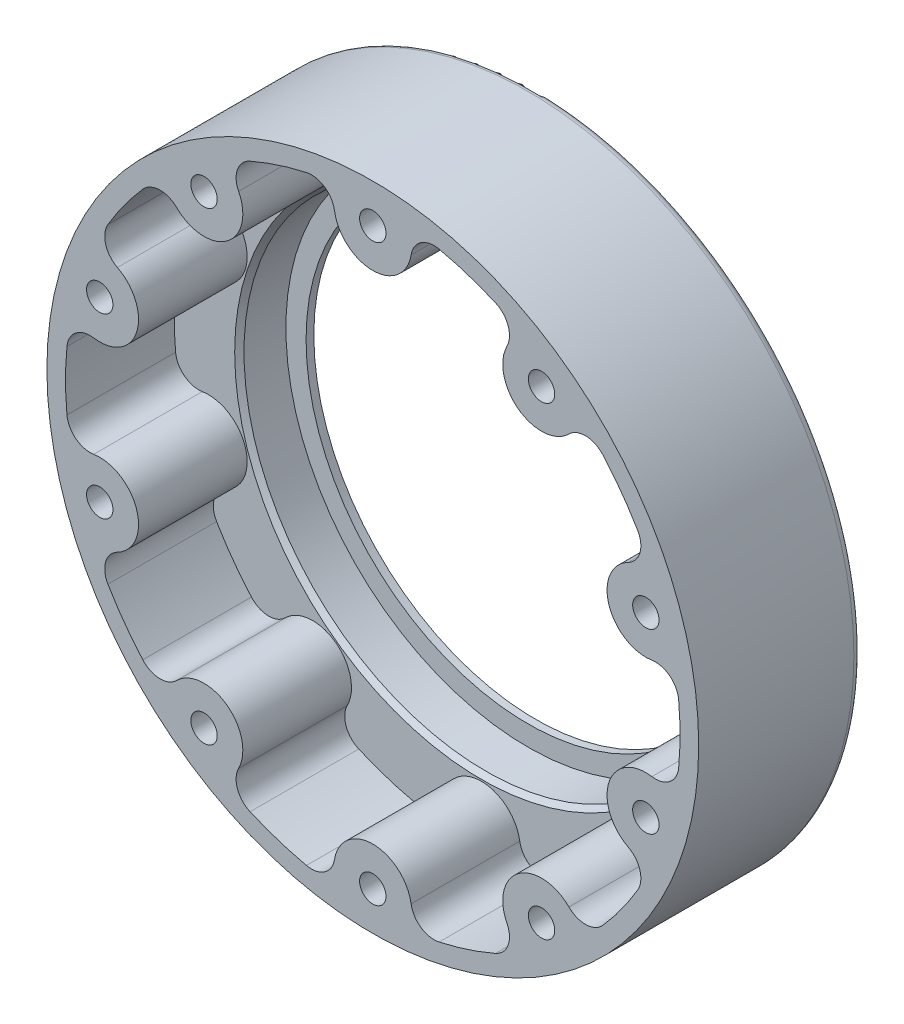
SolidWorks part; units mm, degrees
material "ABS"
ref_plane "Plan de face" through (0, 0, 0) normal (0, 0, 1) x (1, 0, 0)
ref_plane "Plan de dessus" through (0, 0, 0) normal (0, 1, 0) x (1, 0, 0)
ref_plane "Plan de droite" through (0, 0, 0) normal (1, 0, 0) x (0, 0, -1)
sketch "Esquisse1" plane through (0, 0, 0) normal (0, 0, 1) x (1, 0, 0)
  circle A0 centre (0, 0) radius 31.2
  circle A1 centre (0, 0) radius 42
  circle A2 centre (0, 0) radius 37 construction
  circle A3 centre (0, 37) radius 5 construction
  dimension "D1" = 62.4
  dimension "D2" = 10
  dimension "D3" = 74
  dimension "D4" = 84
extrude "Boss.-Extru.1" add sketch "Esquisse1" along normal blind 6
sketch "Esquisse2" plane through (0, 0, 0) normal (0, 0, -1) x (-1, 0, 0)
  circle A0 centre (0, 0) radius 28.6
  circle A1 centre (0, 0) radius 31.2 construction
  circle A2 centre (0, 0) radius 42 construction
  circle A3 centre (0, 0) radius 42
  dimension "D1" = 2.6
extrude "Boss.-Extru.2" add sketch "Esquisse2" along normal blind 1
sketch "Esquisse3" plane through (0, 0, 6) normal (0, 0, 1) x (1, 0, 0)
  circle A0 centre (0, 0) radius 37 construction
  circle A1 centre (0, 37) radius 5
  circle A2 centre (21.7481, 29.9336) radius 5
  circle A3 centre (35.1891, 11.4336) radius 5
  circle A4 centre (35.1891, -11.4336) radius 5
  circle A5 centre (21.7481, -29.9336) radius 5
  circle A6 centre (0, -37) radius 5
  circle A7 centre (-21.7481, -29.9336) radius 5
  circle A8 centre (-35.1891, -11.4336) radius 5
  circle A9 centre (-35.1891, 11.4336) radius 5
  circle A10 centre (-21.7481, 29.9336) radius 5
  point P25 (0, 0)
  dimension "D1" = 74
  dimension "D2" = 10
  dimension "D3" = 10
extrude "Boss.-Extru.3" add sketch "Esquisse3" along normal blind 14
sketch "Esquisse4" plane through (0, 0, 6) normal (0, 0, 1) x (1, 0, 0)
  circle A0 centre (0, 0) radius 39.6
  circle A1 centre (0, 0) radius 42
  arc A2 (-39.9444, 12.9787) -> (-39.9444, -12.9787) centre (0, 0) ccw construction
  dimension "D1" = 2.4
extrude "Boss.-Extru.4" add sketch "Esquisse4" along normal blind 14
fillet "Congé1" radius 3 20 edges at (26.7004, -29.2447, 13) (19.5625, -34.4307, 13) (4.4115, -39.3535, 13) (-19.5625, -34.4307, 13) (-26.7004, -29.2447, 13) (-36.0642, -16.3565, 13) (-38.7906, -7.9654, 13) (-38.7906, 7.9654, 13) (-36.0642, 16.3565, 13) (-26.7004, 29.2447, 13) (-19.5625, 34.4307, 13) (-4.4115, 39.3535, 13) (4.4115, 39.3535, 13) (19.5625, 34.4307, 13) (26.7004, 29.2447, 13) (36.0642, 16.3565, 13) (38.7906, 7.9654, 13) (38.7906, -7.9654, 13) (36.0642, -16.3565, 13) (-4.4115, -39.3535, 13)
sketch "Esquisse5" plane through (0, 0, -1) normal (0, 0, -1) x (-1, 0, 0)
  circle A0 centre (0, 0) radius 37 construction
  circle A1 centre (0, 37) radius 1.7
  circle A2 centre (21.7481, 29.9336) radius 1.7
  circle A3 centre (35.1891, 11.4336) radius 1.7
  circle A4 centre (35.1891, -11.4336) radius 1.7
  circle A5 centre (21.7481, -29.9336) radius 1.7
  circle A6 centre (0, -37) radius 1.7
  circle A7 centre (-21.7481, -29.9336) radius 1.7
  circle A8 centre (-35.1891, -11.4336) radius 1.7
  circle A9 centre (-35.1891, 11.4336) radius 1.7
  circle A10 centre (-21.7481, 29.9336) radius 1.7
  point P25 (0, 0)
  dimension "D1" = 74
  dimension "D2" = 3.4
  dimension "D3" = 10
extrude "Enlèv. mat.-Extru.1" cut sketch "Esquisse5" against normal through all
sketch "Esquisse6" plane through (0, 0, -1) normal (0, 0, -1) x (-1, 0, 0)
  circle A0 centre (0, 37) radius 3
  circle A1 centre (21.7481, 29.9336) radius 3
  circle A2 centre (35.1891, 11.4336) radius 3
  circle A3 centre (35.1891, -11.4336) radius 3
  circle A4 centre (21.7481, -29.9336) radius 3
  circle A5 centre (0, -37) radius 3
  circle A6 centre (-21.7481, -29.9336) radius 3
  circle A7 centre (-35.1891, -11.4336) radius 3
  circle A8 centre (-35.1891, 11.4336) radius 3
  circle A9 centre (-21.7481, 29.9336) radius 3
  point P23 (0, 0)
  dimension "D1" = 6
  dimension "D2" = 10
extrude "Enlèv. mat.-Extru.2" cut sketch "Esquisse6" against normal blind 3.2
chamfer "Chanfrein1" distance 0.6 angle 45 1 edges at (31.2, 0, 6)
fillet "Congé2" radius 1 1 edges at (-42, 0, -1)
